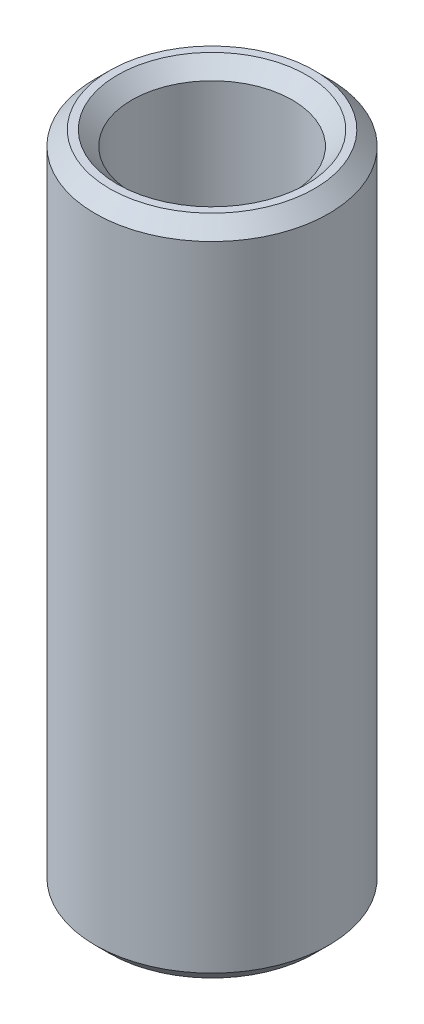
SolidWorks part; units mm, degrees
ref_plane "Front Plane" through (0, 0, 0) normal (0, 0, 1) x (1, 0, 0)
ref_plane "Top Plane" through (0, 0, 0) normal (0, 1, 0) x (1, 0, 0)
ref_plane "Right Plane" through (0, 0, 0) normal (1, 0, 0) x (0, 0, -1)
sketch "Sketch1" plane through (0, 0, 0) normal (0, 1, 0) x (1, 0, 0)
  circle A0 centre (0, 0) radius 27.5
  dimension "SLEEVE_OD" = 55
extrude "Boss-Extrude1" add sketch "Sketch1" along normal blind 155.9657
sketch "Sketch2" plane through (0, 0, 0) normal (0, 1, 0) x (1, 0, 0)
  circle A0 centre (0, 0) radius 18.885
  dimension "BORE_D" = 37.7701
extrude "Cut-Extrude1" cut sketch "Sketch2" along normal through all
chamfer "Chamfer1" distance 3.3896 angle 45 4 edges at (0, 155.9657, 18.885) (0, 0, 18.885) (0, 0, 27.5) (0, 155.9657, 27.5)
